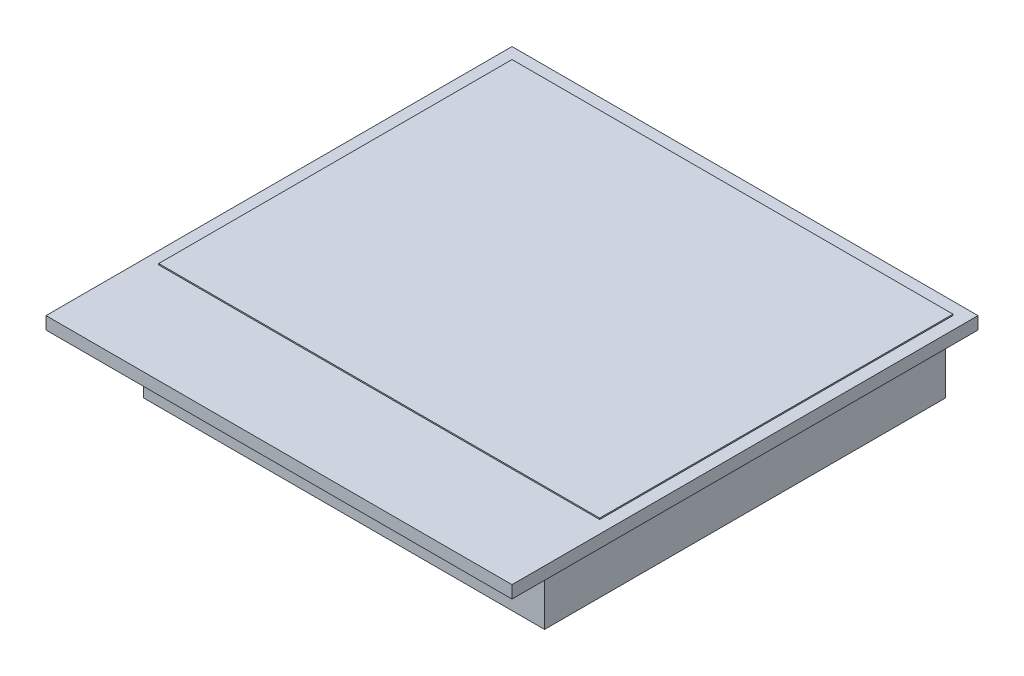
SolidWorks part; units mm, degrees
ref_plane "Front Plane" through (0, 0, 0) normal (0, 0, 1) x (1, 0, 0)
ref_plane "Top Plane" through (0, 0, 0) normal (0, 1, 0) x (1, 0, 0)
ref_plane "Right Plane" through (0, 0, 0) normal (1, 0, 0) x (0, 0, -1)
sketch "Sketch1" plane through (0, 0, 0) normal (0, 1, 0) x (1, 0, 0)
  line L1 (-9.3, 0) -> (9.3, 0)
  line L2 (-9.3, 0) -> (-9.3, 18.6)
  line L3 (-9.3, 18.6) -> (9.3, 18.6)
  line L4 (9.3, 0) -> (9.3, 18.6)
  point P4 (0, 0)
  dimension "D1" = 18.6
  dimension "D2" = 18.6
extrude "glass" add sketch "Sketch1" along normal blind 0.5
sketch "Sketch2" plane through (0, 0.5, 0) normal (0, 1, 0) x (1, 0, 0)
  line L0 (0, 4) -> (0, 0) construction
  line L1 (-8.8, 18.1) -> (8.8, 18.1)
  line L2 (-8.8, 18.1) -> (-8.8, 4)
  line L3 (-8.8, 4) -> (8.8, 4)
  line L4 (8.8, 18.1) -> (8.8, 4)
  line L5 (-9.3, 0) -> (9.3, 0) construction
  line L6 (-9.3, 18.6) -> (-9.3, 0) construction
  line L7 (9.3, 18.6) -> (-9.3, 18.6) construction
  dimension "D1" = 4
  dimension "D2" = 0.5
  dimension "D3" = 0.5
extrude "display" add sketch "Sketch2" along normal blind 0.05 separate body
sketch "Sketch3" plane through (0, 0, 0) normal (0, -1, 0) x (1, 0, 0)
  line L0 (0, 0) -> (0, -2.6) construction
  line L1 (-8, -2.6) -> (8, -2.6)
  line L2 (-8, -2.6) -> (-8, -18.6)
  line L3 (-8, -18.6) -> (8, -18.6)
  line L4 (8, -2.6) -> (8, -18.6)
  line L5 (-9.3, 0) -> (9.3, 0) construction
  line L6 (9.3, -18.6) -> (-9.3, -18.6) construction
  dimension "D1" = 16
  dimension "D2" = 16
extrude "sticky_foam" add sketch "Sketch3" along normal blind 3 separate body
